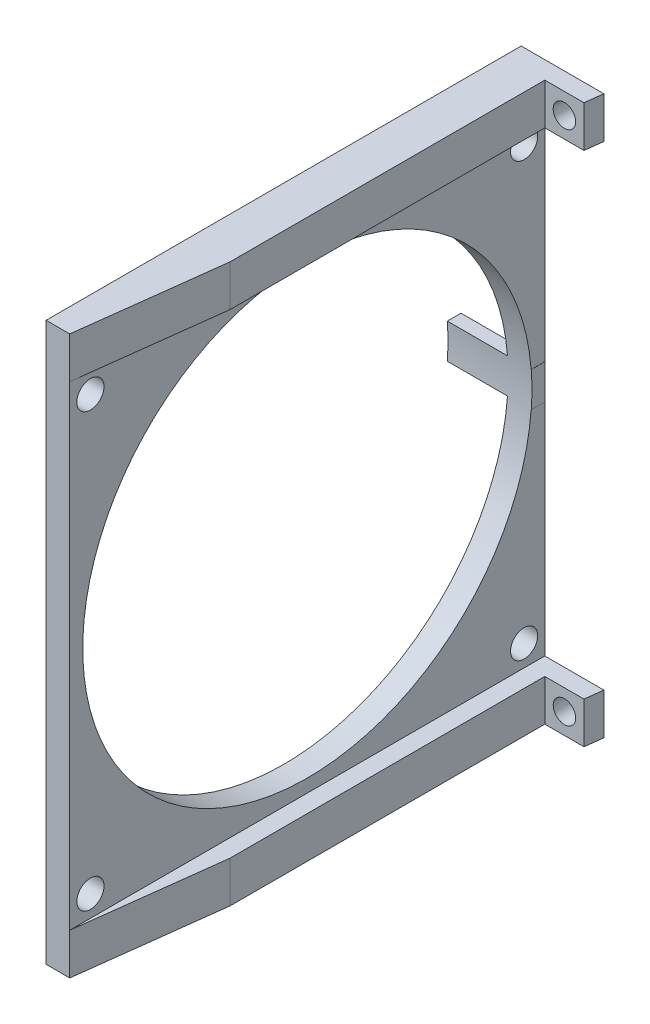
SolidWorks part; units mm, degrees
ref_plane "Front Plane" through (0, 0, 0) normal (0, 0, 1) x (1, 0, 0)
ref_plane "Top Plane" through (0, 0, 0) normal (0, 1, 0) x (1, 0, 0)
ref_plane "Right Plane" through (0, 0, 0) normal (1, 0, 0) x (0, 0, -1)
sketch "Sketch2" plane through (0, 0, 0) normal (0, 1, 0) x (1, 0, 0)
  line L1 (0, 0) -> (4, 0)
  line L2 (0, 0) -> (0, 80.4)
  line L3 (0, 80.4) -> (4, 80.4)
  line L4 (4, 0) -> (4, 80.4)
  dimension "D1" = 80.4
  dimension "D2" = 4
extrude "Boss-Extrude1" add sketch "Sketch2" along normal blind 80.4
sketch "Sketch11" plane through (0, 0, -80.4) normal (0, 0, -1) x (-1, 0, 0)
  line L0 (0, 80.4) -> (0, 0) construction
  line L5 (0, 37.2535) -> (0, 43.1465) construction
  line L6 (-4.0246, 40.2) -> (4.0246, 40.2) construction
  line L8 (-4.0246, 43.1465) -> (10.1883, 43.1465)
  line L9 (-4.0246, 43.1465) -> (-4.0246, 37.2535)
  line L10 (-4.0246, 37.2535) -> (10.1883, 37.2535)
  line L11 (10.1883, 43.1465) -> (10.1883, 37.2535)
  point P0 (0, 40.2)
extrude "Boss-Extrude4" add sketch "Sketch11" against normal blind 4 contours L9 L8 L11 L10
sketch "Sketch3" plane through (4, 0, 0) normal (1, 0, 0) x (0, 0, -1)
  line L0 (40.2, 80.4) -> (40.2, 0) construction
  line L2 (0, 80.4) -> (80.4, 80.4) construction
  line L3 (0, 0) -> (80.4, 0) construction
  line L4 (0, 40.2) -> (80.4, 40.2) construction
  line L5 (0, 80.4) -> (0, 0) construction
  line L6 (80.4, 80.4) -> (80.4, 43.1465) construction
  circle A0 centre (3.5, 76.8) radius 2.3
  circle A1 centre (3.5, 3.6) radius 2.3
  circle A2 centre (76.9, 3.6) radius 2.3
  circle A3 centre (76.9, 76.8) radius 2.3
  circle A4 centre (40.2, 40.2) radius 38
  dimension "D1" = 4.6
sketch "Sketch4" plane through (0, 0, 0) normal (-1, 0, 0) x (0, 0, 1)
  line L1 (-80.4, 0) -> (0, 0)
  line L2 (-80.4, 0) -> (-80.4, -7)
  line L3 (-80.4, -7) -> (0, -7)
  line L4 (0, 0) -> (0, -7)
  line L5 (-80.4, 80.4) -> (0, 80.4)
  line L6 (-80.4, 80.4) -> (-80.4, 87.4)
  line L7 (-80.4, 87.4) -> (0, 87.4)
  line L8 (0, 80.4) -> (0, 87.4)
  dimension "D1" = 7
  dimension "D2" = 7
extrude "Cut-Extrude3" cut sketch "Sketch3" against normal blind 24 and the other way blind 4
extrude "Boss-Extrude3" add sketch "Sketch4" against normal blind 14
sketch "Sketch8" plane through (0, 87.4, 0) normal (0, 1, 0) x (1, 0, 0)
  line L0 (4, 0) -> (14, 0)
  line L1 (4, 0) -> (14, 80.4)
  line L2 (14, 0) -> (14, 80.4)
extrude "Cut-Extrude5" cut sketch "Sketch8" against normal blind 95
sketch "Sketch9" plane through (0, 0, -80.4) normal (0, 0, -1) x (-1, 0, 0)
  line L0 (10.1883, 40.2) -> (-19.4424, 40.2) construction
  line L2 (10.1883, 43.1465) -> (10.1883, 37.2535) construction
  circle A0 centre (-10.3209, 83.9) radius 1.9
  circle A2 centre (-10.3209, -3.5) radius 1.9
extrude "Cut-Extrude6" cut sketch "Sketch9" against normal blind 95
sketch "Sketch10" plane through (0, 87.4, 0) normal (0, 1, 0) x (1, 0, 0)
  line L4 (14, 80.4) -> (4, 0) construction
  line L6 (7, 77.4) -> (13.6269, 77.4)
  line L7 (13.6269, 77.4) -> (7, 24.12)
  line L8 (7, 77.4) -> (7, 24.12)
extrude "Cut-Extrude7" cut sketch "Sketch10" against normal blind 95
sketch "Sketch12" plane through (0, 0, -80.4) normal (0, 0, -1) x (-1, 0, 0)
  circle A0 centre (6.0814, 40.2) radius 1.9
  dimension "D1" = 3.8
equation "\"D2@Sketch4\"=\"D1@Sketch4\""
